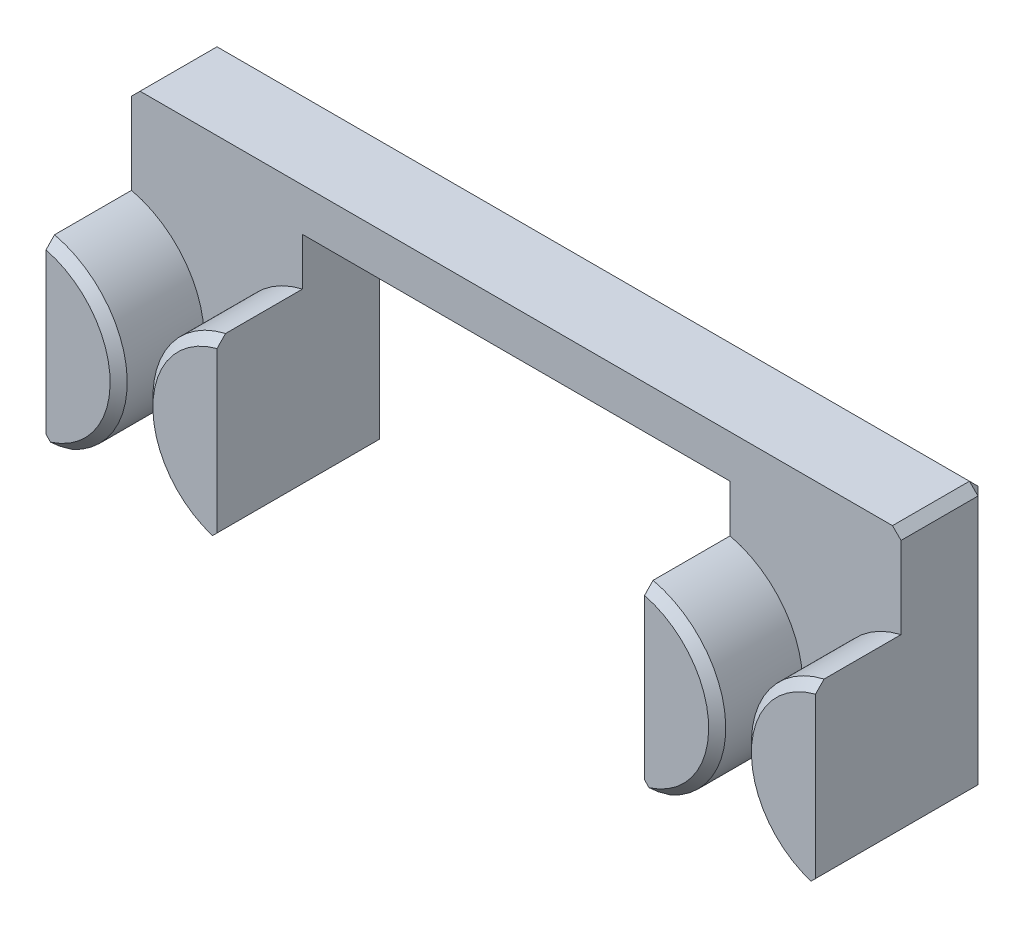
SolidWorks part; units mm, degrees
ref_plane "Front" through (0, 0, 0) normal (0, 0, 1) x (1, 0, 0)
ref_plane "Top" through (0, 0, 0) normal (0, 1, 0) x (1, 0, 0)
ref_plane "Right" through (0, 0, 0) normal (1, 0, 0) x (0, 0, -1)
sketch "Sketch1" plane through (0, 0, 0) normal (0, 0, 1) x (1, 0, 0)
  line L0 (-9, 3.125) -> (9, 3.125)
  line L5 (9, 3.125) -> (9, -3.125)
  line L6 (9, -3.125) -> (5, -3.125)
  line L7 (5, -3.125) -> (5, 2.125)
  line L8 (5, 2.125) -> (-5, 2.125)
  line L9 (-5, 2.125) -> (-5, -3.125)
  line L10 (-5, -3.125) -> (-9, -3.125)
  line L11 (-9, -3.125) -> (-9, 3.125)
  line L12 (8.3642, -3.125) -> (5.6358, -3.125) construction
extrude "Boss-Extrude1" add sketch "Sketch1" against normal blind 2
sketch "Sketch2" plane through (0, 0, 0) normal (0, 0, 1) x (1, 0, 0)
  line L0 (9, 3.125) -> (9, -3.125) construction
  line L1 (9, 3.125) -> (9, -3.125)
  line L2 (9, -3.125) -> (5, -3.125) construction
  line L3 (9, -3.125) -> (5, -3.125)
  circle A1 centre (9.5, -1.125) radius 2.3
  circle A2 centre (9.5, -1.125) radius 2.3
  circle A4 centre (9.5, -1.125) radius 2.2
  circle A5 centre (9.5, -1.125) radius 2.2
  dimension "D1" = 0
  dimension "D2" = 0.1
extrude "Boss-Extrude2" add sketch "Sketch2" along normal blind 2 contours A5 region at (8.2874, -1.1125, 0)
ref_plane "Plane1" through (7, 0, 0) normal (1, 0, 0) x (0, 0, -1)
mirror "Mirror1" about plane through (7, 0, 0) normal (1, 0, 0) of "Boss-Extrude2"
mirror "Mirror2" about plane through (0, 0, 0) normal (1, 0, 0) of "Mirror1"
chamfer "Deburs" distance 0.2 angle 45 18 edges at (0, 3.125, -2) (9, 3.125, -1) (9, 0, -2) (9, -3.125, 0) (7, -3.125, -2) (5, -3.125, 0) (5, -0.5, -2) (0, 2.125, -2) (-5, -0.5, -2) (-5, -3.125, 0) (-7, -3.125, -2) (-9, 3.125, -1) (-9, 0, -2) (-9, -3.125, 0) (7.311, -0.9049, 2) (6.689, -0.9049, 2) (-6.689, -0.9049, 2) (-7.311, -0.9049, 2)
